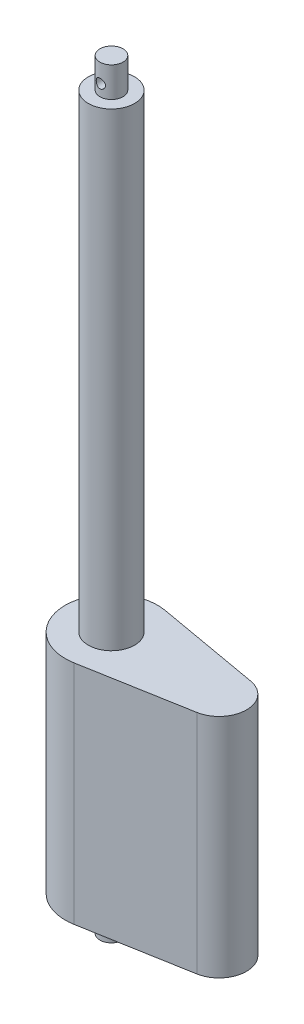
SolidWorks part; units mm, degrees
ref_plane "Front" through (0, 0, 0) normal (0, 0, 1) x (1, 0, 0)
ref_plane "Top" through (0, 0, 0) normal (0, 1, 0) x (1, 0, 0)
ref_plane "Right" through (0, 0, 0) normal (1, 0, 0) x (0, 0, -1)
sketch "Sketch7" plane through (0, 0, 0) normal (1, 0, 0) x (0, 0, -1)
  line L1 (-20, 7) -> (-20, 105)
  line L4 (-10, 308) -> (-5, 308)
  line L5 (-5, 308) -> (-5, 321)
  line L6 (-5, 321) -> (0, 321)
  line L7 (0, 321) -> (0, -8)
  line L9 (-5, -8) -> (0, -8)
  line L10 (-10, 308) -> (-10, 105)
  line L11 (-10, 105) -> (-20, 105)
  line L12 (-5, -8) -> (-5, 7)
  line L13 (-5, 7) -> (-20, 7)
  point P11 (0, 0)
  point P12 (0, 313)
  point P13 (0, 320)
  dimension "D1" = 8
  dimension "D2" = 8
  dimension "D3" = 98
  dimension "D5" = 12
  dimension "D7" = 10
  dimension "D8" = 20
  dimension "D11" = 5
  dimension "D9" = 15
  dimension "D10" = 5
  dimension "D4" = 1
  dimension "D6" = 320
revolve "Revolve2" add sketch "Sketch7" angle 360 about L7
sketch "Sketch8" plane through (0, 0, 0) normal (0, 0, 1) x (1, 0, 0)
  line L0 (-5, -8) -> (5, -8) construction
  line L2 (0, 321) -> (0, 313) construction
  line L3 (5, 321) -> (-5, 321) construction
  line L4 (-5, -8) -> (5, -8) construction
  line L5 (0, -8) -> (0, 0) construction
  circle A1 centre (0, 313) radius 2
  circle A2 centre (0, 0) radius 2
  dimension "D2" = 8
  dimension "D1" = 4
  dimension "D4" = 4
  dimension "D3" = 8
extrude "Cut-Extrude2" cut sketch "Sketch8" against normal through all and the other way through all
sketch "Sketch10" plane through (0, 105, 0) normal (0, 1, 0) x (1, 0, 0)
  line L0 (0, 0) -> (46.5567, 0) construction
  line L1 (3.491, 19.693) -> (48.6292, 11.6912)
  line L2 (48.6292, -11.6912) -> (3.491, -19.693)
  circle A1 centre (0, 0) radius 20 construction
  arc A2 (48.6292, 11.6912) -> (48.6292, -11.6912) centre (46.5567, 0) cw
  arc A3 (3.491, 19.693) -> (3.491, -19.693) centre (0, 0) ccw
extrude "Boss-Extrude4" add sketch "Sketch10" against normal up to surface (98 mm away) up to face at (0, 7, 5)
sketch "Sketch11" plane through (0, 0, 0) normal (0, 0, 1) x (1, 0, 0)
  line L0 (0, 313) -> (0, 0)
equation "\"mountingHoleDistance\"=8"
equation "\"actuatorLength\"= 1"
equation "\"D1@Sketch7\"= \"mountingHoleDistance\""
equation "\"D2@Sketch7\"=\"mountingHoleDistance\""
equation "\"MotorHousingHeight\"= 98"
equation "\"D3@Sketch7\"=\"MotorHousingHeight\""
equation "\"acutatorMinimumLength\"= 320"
equation "\"D3@Sketch8\"=\"mountingHoleDistance\""
equation "\"D2@Sketch8\"=\"mountingHoleDistance\""
equation "\"D4@Sketch7\"=\"actuatorLength\""
equation "\"D6@Sketch7\"=\"acutatorMinimumLength\""
